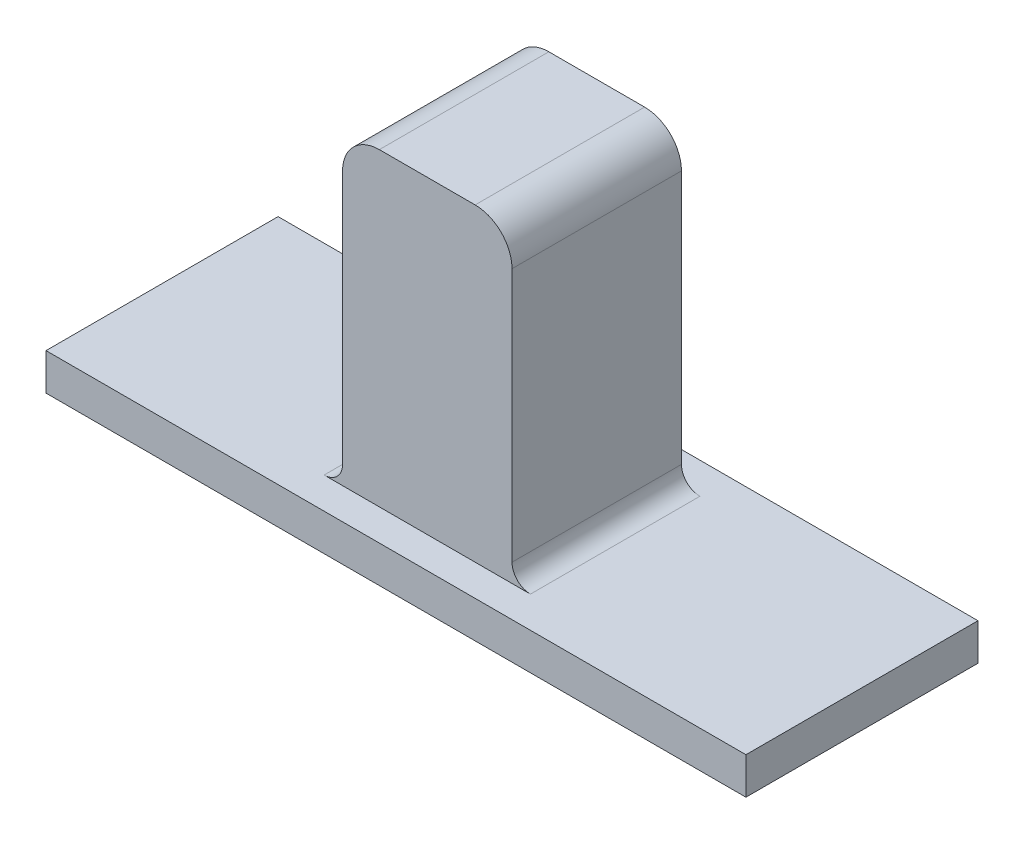
SolidWorks part; units mm, degrees
ref_plane "Front Plane" through (0, 0, 0) normal (0, 0, 1) x (1, 0, 0)
ref_plane "Top Plane" through (0, 0, 0) normal (0, 1, 0) x (1, 0, 0)
ref_plane "Right Plane" through (0, 0, 0) normal (1, 0, 0) x (0, 0, -1)
sketch "Sketch1" plane through (0, 0, 0) normal (0, 1, 0) x (1, 0, 0)
  line L0 (1.7304, 1.0963) -> (1.7304, 1.6562)
  line L1 (-6.9196, 3.9562) -> (12.0804, 3.9562)
  line L2 (-6.9196, 3.9562) -> (-6.9196, -2.3438)
  line L3 (-6.9196, -2.3438) -> (12.0804, -2.3438)
  line L4 (12.0804, 3.9562) -> (12.0804, -2.3438)
  line L5 (1.7304, 1.6562) -> (2.2825, 1.6562)
  line L6 (2.8681, 1.6562) -> (3.4304, 1.6562)
  line L7 (3.4304, 1.6562) -> (3.4304, 1.0963)
  line L8 (2.3215, -0.0438) -> (1.7304, -0.0438)
  line L9 (0.2804, 3.1062) -> (4.8804, 3.1062)
  line L10 (0.2804, 3.1062) -> (0.2804, -1.4938)
  line L11 (0.2804, -1.4938) -> (4.8804, -1.4938)
  line L12 (4.8804, 3.1062) -> (4.8804, -1.4938)
  line L13 (1.7304, -0.0438) -> (1.7304, 0.5256)
  line L14 (3.4304, 0.5256) -> (3.4304, -0.0438)
  line L15 (3.4304, -0.0438) -> (2.8681, -0.0438)
  line L18 (2.8681, 1.6562) -> (2.8681, 1.5562)
  line L19 (2.8681, 1.5562) -> (2.2825, 1.5562)
  line L20 (2.2825, 1.6562) -> (2.2825, 1.5562)
  line L21 (1.7304, 1.0963) -> (1.8304, 1.0963)
  line L23 (1.7304, 0.5256) -> (1.8304, 0.5256)
  line L24 (1.8304, 1.0963) -> (1.8304, 0.5256)
  line L26 (2.3215, -0.0438) -> (2.3215, 0.0562)
  line L27 (2.3215, 0.0562) -> (2.8681, 0.0562)
  line L28 (2.8681, -0.0438) -> (2.8681, 0.0562)
  line L29 (3.3304, 0.5256) -> (3.4304, 0.5256)
  line L30 (3.3304, 0.5256) -> (3.3304, 1.0963)
  line L31 (3.3304, 1.0963) -> (3.4304, 1.0963)
  point P8 (2.5804, 3.9562)
  point P10 (12.0804, 0.8062)
  point P11 (2.5804, 0.8062)
  dimension "D1" = 19
  dimension "D2" = 6.3
  dimension "D7" = 0
  dimension "D8" = 0
  dimension "D9" = 2.3
  dimension "D10" = 4.6
  dimension "D11" = 2.3
  dimension "D12" = 4.6
extrude "Boss-Extrude1" add sketch "Sketch1" along normal blind 1 contours L3 L4 L1 L2
extrude "Boss-Extrude2" add sketch "Sketch1<3>" along normal blind 9.4 contours L11 L12 L9 L10
sketch "Sketch1<3>" plane through (0, 0, 0) normal (0, 1, 0) x (1, 0, 0) same geometry as "Sketch1"
fillet "Fillet6" radius 1 1 edges at (4.8804, 9.4, -0.8062)
fillet "Fillet7" radius 1 1 edges at (0.2804, 9.4, -0.8062)
fillet "Fillet9" radius 0.5 1 edges at (4.8804, 1, -0.8062)
fillet "Fillet10" radius 0.5 1 edges at (0.2804, 1, -0.8062)
extrude "Cut-Extrude6" cut sketch "Sketch1<6>" along normal blind 3 contours L30 L31 L7 L6 L18 L19 L20 L5 L0 L21 L24 L23 L13 L8 L26 L27 L28 L15 L14 L29 region at (2.5802, 0, -0.8048)
sketch "Sketch1<6>" plane through (0, 0, 0) normal (0, 1, 0) x (1, 0, 0) same geometry as "Sketch1"
